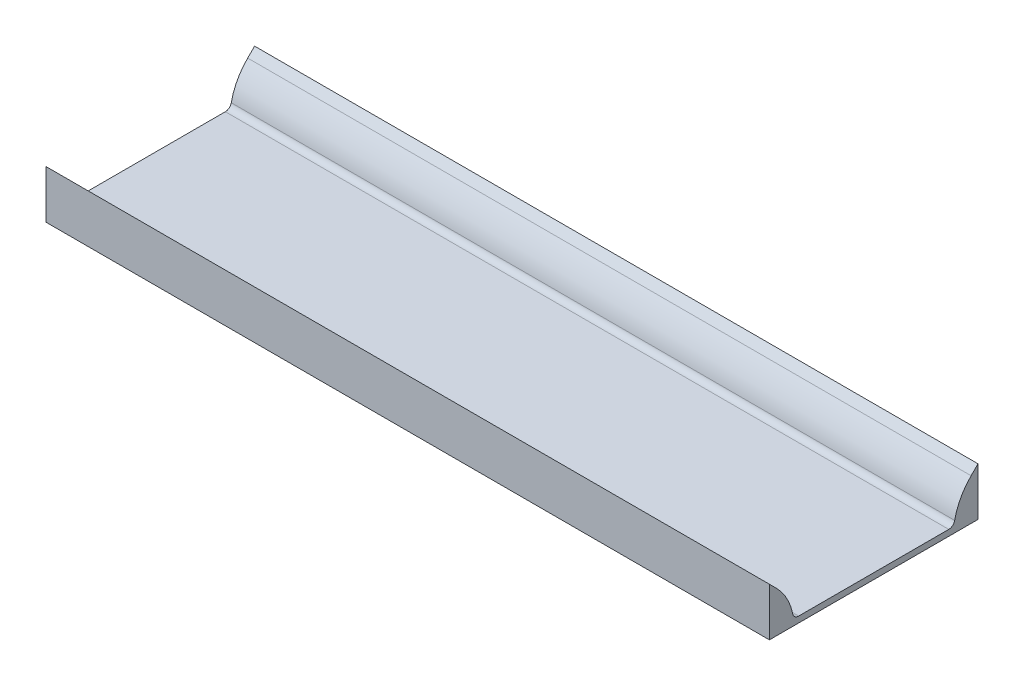
SolidWorks part; units mm, degrees
ref_plane "Front Plane" through (0, 0, 0) normal (0, 0, 1) x (1, 0, 0)
ref_plane "Top Plane" through (0, 0, 0) normal (0, 1, 0) x (1, 0, 0)
ref_plane "Right Plane" through (0, 0, 0) normal (1, 0, 0) x (0, 0, -1)
sketch "Sketch1" plane through (0, 0, 0) normal (0, 1, 0) x (1, 0, 0)
  line L1 (-76.2, 21.971) -> (76.2, 21.971)
  line L2 (-76.2, 21.971) -> (-76.2, -21.971)
  line L3 (-76.2, -21.971) -> (76.2, -21.971)
  line L4 (76.2, 21.971) -> (76.2, -21.971)
  line L5 (-76.2, 21.971) -> (76.2, -21.971) construction
  line L6 (-76.2, -21.971) -> (76.2, 21.971) construction
  point P0 (0, 0)
  dimension "D1" = 43.942
  dimension "D2" = 152.4
extrude "Boss-Extrude1" add sketch "Sketch1" along normal blind 10.16
sketch "Sketch2" plane through (0, 10.16, 0) normal (0, 1, 0) x (1, 0, 0)
  line L0 (76.2, -21.971) -> (76.2, 21.971) construction
  line L1 (-69.85, 16.891) -> (69.85, 16.891)
  line L2 (-69.85, 16.891) -> (-69.85, -16.891)
  line L3 (-69.85, -16.891) -> (69.85, -16.891)
  line L4 (69.85, 16.891) -> (69.85, -16.891)
  line L5 (-69.85, 16.891) -> (69.85, -16.891) construction
  line L6 (-69.85, -16.891) -> (69.85, 16.891) construction
  line L7 (76.2, 21.971) -> (-76.2, 21.971) construction
  line L8 (-76.2, 21.971) -> (-76.2, -21.971) construction
  line L9 (69.85, 16.891) -> (76.2, 16.891)
  line L10 (69.85, 16.891) -> (69.85, -16.891)
  line L11 (69.85, -16.891) -> (76.2, -16.891)
  line L12 (76.2, 16.891) -> (76.2, -16.891)
  line L13 (-69.85, 16.891) -> (-76.2, 16.891)
  line L14 (-69.85, 16.891) -> (-69.85, -16.891)
  line L15 (-69.85, -16.891) -> (-76.2, -16.891)
  line L16 (-76.2, 16.891) -> (-76.2, -16.891)
  point P0 (0, 0)
  line M5 (76.2, -21.971) -> (76.2, 21.971)
  line M7 (-76.2, 21.971) -> (-76.2, -21.971)
  dimension "D1" = 6.35
  dimension "D2" = 5.08
extrude "Cut-Extrude1" cut sketch "Sketch2" against normal blind 8.89 contours L4 L1 L2 L3 | L4 L11 L9 M5 | L15 L2 L13 M7 region at (0, 10.16, 0) region at (-73.025, 10.16, 0) region at (73.025, 10.16, 0)
chamfer "Chamfer1" distance 5.08 angle 45 2 edges at (0, 10.16, 16.891) (0, 10.16, -16.891)
fillet "Fillet1" radius 12.7 2 edges at (0, 5.08, 16.891) (0, 5.08, -16.891)
sketch "Sketch3" plane through (0, 0, 21.971) normal (0, 0, 1) x (1, 0, 0)
  line L0 (-63.5, 0) -> (63.5, 0)
  line L1 (-63.5, 0) -> (-63.5, 5.08)
  line L2 (-76.2, 10.16) -> (-76.2, 0) construction
  line L3 (63.5, 0) -> (63.5, 4.4369)
  line L4 (76.2, 10.16) -> (76.2, 0) construction
  point P8 (-63.6764, 4.9173)
  point P9 (63.8171, 4.7386)
  dimension "D1" = 5.08
extrude "Boss-Extrude2" [suppressed] add sketch "Sketch3" against normal blind 43.18
fillet "Fillet2" radius 1.27 2 edges at (0, 1.27, 16.891) (0, 1.27, -16.891)
